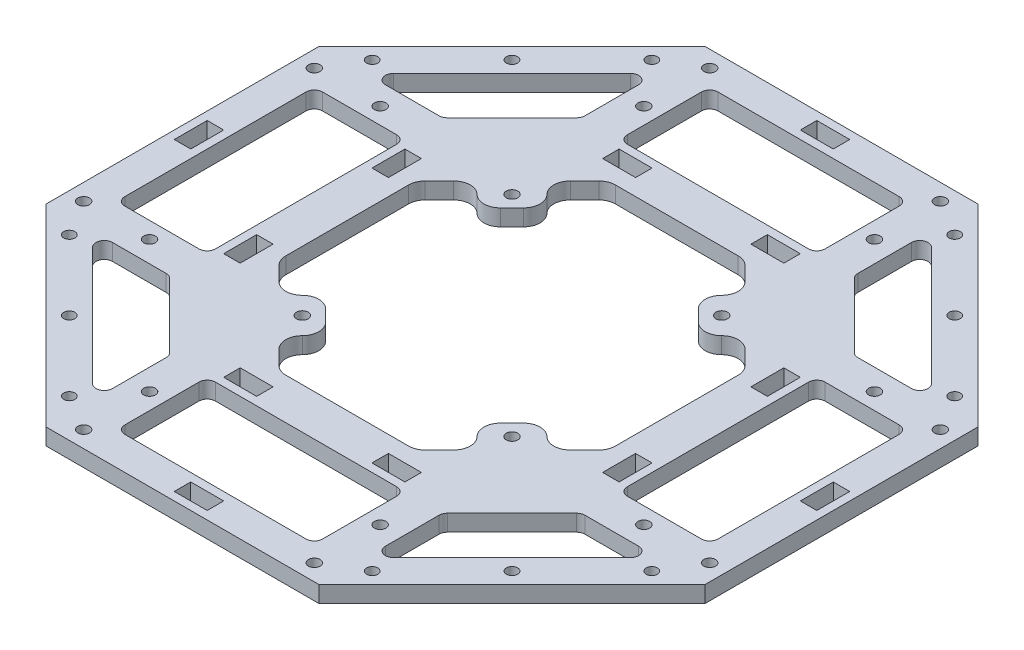
SolidWorks part; units mm, degrees
material "Custom Plastic"
ref_plane "Front Plane" through (0, 0, 0) normal (0, 0, 1) x (1, 0, 0)
ref_plane "Top Plane" through (0, 0, 0) normal (0, 1, 0) x (1, 0, 0)
ref_plane "Right Plane" through (0, 0, 0) normal (1, 0, 0) x (0, 0, -1)
ref_axis "Axis1" through (0, -0.2997, 0) along (0, 1, 0)
sketch "Base sketch" plane through (0, 0, 0) normal (0, 1, 0) x (1, 0, 0)
  line L1 (-127, 52.6051) -> (-127, -52.6051)
  line L2 (-127, -52.6051) -> (-52.6051, -127)
  line L3 (-52.6051, -127) -> (52.6051, -127)
  line L4 (52.6051, -127) -> (127, -52.6051)
  line L5 (127, -52.6051) -> (127, 52.6051)
  line L6 (127, 52.6051) -> (52.6051, 127)
  line L7 (52.6051, 127) -> (-52.6051, 127)
  line L8 (-52.6051, 127) -> (-127, 52.6051)
  circle A0 centre (0, 0) radius 127 construction
  dimension "D1" = 254
extrude "Base" add sketch "Base sketch" along normal blind 6.35
sketch "Sketch3" plane through (0, 6.35, 0) normal (0, 1, 0) x (1, 0, 0)
  line L0 (52.6051, 127) -> (-52.6051, 127) construction
  line L1 (-38.1, 114.3) -> (38.1, 114.3)
  line L2 (-38.1, 114.3) -> (-38.1, 79.375)
  line L4 (-38.1, 79.375) -> (38.1, 79.375)
  line L5 (38.1, 114.3) -> (38.1, 79.375)
  point P6 (0, 79.375)
  dimension "D1" = 76.2
  dimension "D2" = 34.925
  dimension "D3" = 12.7
extrude "Wheel cutout" cut sketch "Sketch3" against normal up to next
fillet "Wheel cutout fillets" radius 3.175 4 edges at (38.1, 3.175, -114.3) (38.1, 3.175, -79.375) (-38.1, 3.175, -79.375) (-38.1, 3.175, -114.3)
pattern_circular "Wheel cutout pattern" count 4 over 360 about axis through (0, -0.2997, 0) along (0, 1, 0) of "Wheel cutout", "Wheel cutout fillets"
sketch "Sketch4" plane through (0, 6.35, 0) normal (0, 1, 0) x (1, 0, 0)
  line L0 (0, 0) -> (0, 127) construction
  line L1 (52.6051, 127) -> (-52.6051, 127) construction
  line L2 (34.925, 120.65) -> (-34.925, 120.65) construction
  line L3 (-34.925, 123.825) -> (-22.225, 123.825) construction
  line L4 (-34.925, 123.825) -> (-34.925, 117.475) construction
  line L5 (-34.925, 117.475) -> (-22.225, 117.475) construction
  line L6 (-22.225, 123.825) -> (-22.225, 117.475) construction
  line L7 (-34.925, 123.825) -> (-22.225, 117.475) construction
  line L8 (-34.925, 117.475) -> (-22.225, 123.825) construction
  line L9 (34.925, 114.3) -> (-34.925, 114.3) construction
  line L10 (34.925, 117.475) -> (22.225, 123.825) construction
  line L11 (34.925, 123.825) -> (22.225, 117.475) construction
  line L12 (22.225, 123.825) -> (22.225, 117.475) construction
  line L13 (34.925, 117.475) -> (22.225, 117.475) construction
  line L14 (34.925, 123.825) -> (34.925, 117.475) construction
  line L15 (34.925, 123.825) -> (22.225, 123.825) construction
  line L16 (-38.1, 96.8375) -> (38.1, 96.8375) construction
  line L17 (-38.1, 111.125) -> (-38.1, 82.55) construction
  line L18 (38.1, 82.55) -> (38.1, 111.125) construction
  line L19 (34.925, 69.85) -> (22.225, 76.2) construction
  line L20 (34.925, 76.2) -> (22.225, 69.85) construction
  line L21 (-34.925, 76.2) -> (-22.225, 69.85) construction
  line L22 (-34.925, 69.85) -> (-22.225, 76.2) construction
  line L23 (34.925, 73.025) -> (-34.925, 73.025) construction
  line L24 (34.925, 69.85) -> (22.225, 69.85)
  line L25 (34.925, 69.85) -> (34.925, 76.2)
  line L26 (34.925, 76.2) -> (22.225, 76.2)
  line L27 (22.225, 69.85) -> (22.225, 76.2)
  line L28 (-22.225, 69.85) -> (-22.225, 76.2)
  line L29 (-34.925, 76.2) -> (-22.225, 76.2)
  line L30 (-34.925, 69.85) -> (-34.925, 76.2)
  line L31 (-34.925, 69.85) -> (-22.225, 69.85)
  line L33 (-6.35, 117.475) -> (6.35, 117.475)
  line L34 (-6.35, 117.475) -> (-6.35, 123.825)
  line L35 (-6.35, 123.825) -> (6.35, 123.825)
  line L36 (6.35, 117.475) -> (6.35, 123.825)
  line L37 (-6.35, 117.475) -> (6.35, 123.825) construction
  line L38 (-6.35, 123.825) -> (6.35, 117.475) construction
  point P5 (-28.575, 120.65)
  point P12 (0, 120.65)
  point P17 (28.575, 120.65)
  point P34 (28.575, 73.025)
  point P35 (-28.575, 73.025)
  point P38 (0, 120.65)
  dimension "D1" = 6.35
  dimension "D2" = 12.7
  dimension "D3" = 69.85
  dimension "D4" = 6.35
  dimension "D5" = 12.7
  dimension "D6" = 6.35
extrude "Support cutouts" cut sketch "Sketch4" against normal up to next
pattern_circular "Support cutout pattern" count 4 over 360 about axis through (0, -0.2997, 0) along (0, 1, 0) of "Support cutouts"
sketch "Sketch9" plane through (0, 6.35, 0) normal (0, 1, 0) x (1, 0, 0)
  line L0 (-109.0395, 52.6051) -> (-52.6051, 109.0395)
  line L1 (-52.6051, 109.0395) -> (-52.6051, 79.375)
  line L2 (-52.6051, 79.375) -> (-79.375, 52.6051)
  line L3 (-79.375, 52.6051) -> (-109.0395, 52.6051)
  line L4 (-52.6051, 127) -> (-127, 52.6051) construction
  line L9 (-79.375, -34.925) -> (-79.375, 34.925) construction
  dimension "D1" = 12.7
extrude "Lightening hole" cut sketch "Sketch9" against normal through all
fillet "Fillet2" radius 3.175 4 edges at (-52.6051, 3.175, -79.375) (-79.375, 3.175, -52.6051) (-109.0395, 3.175, -52.6051) (-52.6051, 3.175, -109.0395)
pattern_circular "Lightening hole pattern" count 4 over 360 about axis through (0, -0.2997, 0) along (0, 1, 0) of "Lightening hole", "Fillet2"
sketch "Sketch17" plane through (0, 6.35, 0) normal (0, 1, 0) x (1, 0, 0)
  line L1 (-63.5, 26.3026) -> (-63.5, -26.3026)
  line L2 (-63.5, -26.3026) -> (-26.3026, -63.5)
  line L3 (-26.3026, -63.5) -> (26.3026, -63.5)
  line L4 (26.3026, -63.5) -> (63.5, -26.3026)
  line L5 (63.5, -26.3026) -> (63.5, 26.3026)
  line L6 (63.5, 26.3026) -> (26.3026, 63.5)
  line L7 (26.3026, 63.5) -> (-26.3026, 63.5)
  line L8 (-26.3026, 63.5) -> (-63.5, 26.3026)
  circle A0 centre (0, 0) radius 63.5 construction
  dimension "D1" = 127
extrude "Cut-Extrude1" cut sketch "Sketch17" against normal up to next
sketch "Sketch18" plane through (0, 6.35, 0) normal (0, 1, 0) x (1, 0, 0)
  line L0 (-38.1661, 51.6365) -> (-29.1858, 42.6562)
  line L1 (-26.3026, 63.5) -> (-63.5, 26.3026) construction
  line L2 (-29.1858, 42.6562) -> (-42.6562, 29.1858)
  line L3 (-42.6562, 29.1858) -> (-51.6365, 38.1661)
  line L4 (-51.6365, 38.1661) -> (-38.1661, 51.6365)
  line L5 (0, 0) -> (-89.8026, 89.8026) construction
  line L6 (-52.6051, 127) -> (-127, 52.6051) construction
  point P11 (-44.9013, 44.9013)
  dimension "D1" = 19.05
  dimension "D2" = 12.7
extrude "Light sensor mount" add sketch "Sketch18" against normal through all
pattern_circular "CirPattern1" count 4 over 360 about axis through (0, -0.2997, 0) along (0, 1, 0) of "Light sensor mount"
sketch "Sketch19" plane through (0, 6.35, 0) normal (0, 1, 0) x (1, 0, 0)
  line L0 (0, 0) -> (-89.8026, 89.8026) construction
  line L1 (-52.6051, 127) -> (-127, 52.6051) construction
  line L2 (-42.6562, 29.1858) -> (-29.1858, 42.6562) construction
  point P5 (-40.4112, 40.4112)
  point P10 (-49.3914, 49.3914)
  point P11 (-58.3717, 58.3717)
  point P12 (-67.3519, 67.3519)
  dimension "D1" = 6.35
  dimension "D2" = 4
  dimension "D3" = 12.7
hole_wizard "Line tracker mounting holes" positions "Sketch21" profile "Sketch20" hole size "#8" standard "ANSI Inch" end condition up to next
sketch "Sketch21" plane through (0, 6.35, 0) normal (0, 1, 0) x (1, 0, 0)
  point P0 (-40.4112, 40.4112)
sketch "Sketch20" plane through (-40.4112, 6.35, -40.4112) normal (1, 0, 0) x (0, 0, 1)
  line L0 (0, 0) -> (0, 6.351)
  line L1 (0, 6.351) -> (2.2479, 6.351)
  line L2 (2.2479, 6.351) -> (2.2479, 0)
  line L5 (2.2479, 0) -> (0, 0)
  line L11 (0, -6.35) -> (0, 107.95) construction
  dimension "Thru Hole Dia." = 4.4958
  dimension "Thru Hole Depth" = 6.351
pattern_circular "CirPattern2" count 4 over 360 about axis through (0, -0.2997, 0) along (0, 1, 0) of "Line tracker mounting holes"
fillet "Fillet3" radius 6.35 24 edges at (26.3026, 3.175, -63.5) (38.1661, 3.175, -51.6365) (29.1858, 3.175, -42.6562) (42.6562, 3.175, -29.1858) (51.6365, 3.175, -38.1661) (63.5, 3.175, -26.3026) (63.5, 3.175, 26.3026) (51.6365, 3.175, 38.1661) (42.6562, 3.175, 29.1858) (29.1858, 3.175, 42.6562) (38.1661, 3.175, 51.6365) (26.3026, 3.175, 63.5) (-26.3026, 3.175, 63.5) (-38.1661, 3.175, 51.6365) (-29.1858, 3.175, 42.6562) (-42.6562, 3.175, 29.1858) (-51.6365, 3.175, 38.1661) (-63.5, 3.175, 26.3026) (-63.5, 3.175, -26.3026) (-51.6365, 3.175, -38.1661) (-29.1858, 3.175, -42.6562) (-38.1661, 3.175, -51.6365) (-26.3026, 3.175, -63.5) (-42.6562, 3.175, -29.1858)
sketch "Sketch22" plane through (0, 6.35, 0) normal (0, 1, 0) x (1, 0, 0)
  line L0 (0, -127) -> (0, 0) construction
  line L1 (-44.45, -95.25) -> (44.45, -95.25) construction
  line L2 (-44.45, -95.25) -> (-44.45, -120.65) construction
  line L3 (-44.45, -120.65) -> (44.45, -120.65) construction
  line L4 (44.45, -95.25) -> (44.45, -120.65) construction
  line L5 (-52.6051, -127) -> (52.6051, -127) construction
  point P9 (0, -95.25)
  dimension "D1" = 6.35
  dimension "D2" = 88.9
  dimension "D3" = 25.4
hole_wizard "Aligner mounting holes" positions "Sketch24" profile "Sketch23" hole size "#8" standard "ANSI Inch" end condition up to next
sketch "Sketch24" plane through (0, 6.35, 0) normal (0, 1, 0) x (1, 0, 0)
  point P0 (-44.45, -95.25)
  point P3 (-44.45, -120.65)
  point P6 (44.45, -120.65)
  point P9 (44.45, -95.25)
sketch "Sketch23" plane through (-44.45, 6.35, 95.25) normal (1, 0, 0) x (0, 0, 1)
  line L0 (0, 0) -> (0, 6.351)
  line L1 (0, 6.351) -> (2.2479, 6.351)
  line L2 (2.2479, 6.351) -> (2.2479, 0)
  line L5 (2.2479, 0) -> (0, 0)
  line L11 (0, -6.35) -> (0, 107.95) construction
  dimension "Thru Hole Dia." = 4.4958
  dimension "Thru Hole Depth" = 6.351
pattern_circular "CirPattern3" count 4 over 360 about axis through (0, -0.2997, 0) along (0, 1, 0) of "Aligner mounting holes"
sketch "Sketch26" plane through (0, 6.35, 0) normal (0, 1, 0) x (1, 0, 0)
  line L0 (-89.8026, 89.8026) -> (0, 0) construction
  line L1 (-52.6051, 127) -> (-127, 52.6051) construction
  line L2 (-112.2532, 58.3717) -> (-58.3717, 112.2532) construction
  point P5 (-85.3124, 85.3124)
  point P8 (-85.3124, 85.3124)
  dimension "D1" = 6.35
  dimension "D2" = 76.2
hole_wizard "#8 Clearance Hole2" positions "Sketch28" profile "Sketch27" hole size "#8" standard "ANSI Inch" end condition through all
sketch "Sketch28" plane through (0, 6.35, 0) normal (0, 1, 0) x (1, 0, 0)
  line L0 (-112.2532, 58.3717) -> (-58.3717, 112.2532) construction
  point P0 (-58.3717, 112.2532)
  point P3 (-85.3124, 85.3124)
  point P7 (-112.2532, 58.3717)
sketch "Sketch27" plane through (-58.3717, 6.35, -112.2532) normal (1, 0, 0) x (0, 0, 1)
  line L0 (0, 0) -> (0, 6.35)
  line L1 (0, 6.35) -> (2.1526, 6.35)
  line L2 (2.1526, 6.35) -> (2.1526, 0)
  line L5 (2.1526, 0) -> (0, 0)
  line L11 (0, -6.35) -> (0, 107.95) construction
  dimension "Thru Hole Dia." = 4.3053
  dimension "Thru Hole Depth" = 6.35
pattern_circular "CirPattern4" count 4 over 360 about axis through (0, -0.2997, 0) along (0, 1, 0) of "#8 Clearance Hole2"
equation "\"MAT_THICKNESS\"=0.25"
equation "\"D1@Sketch4\"=\"MAT_THICKNESS\""
equation "\"D1@Base\"=\"MAT_THICKNESS\""
equation "\"D6@Sketch4\"=\"MAT_THICKNESS\""
